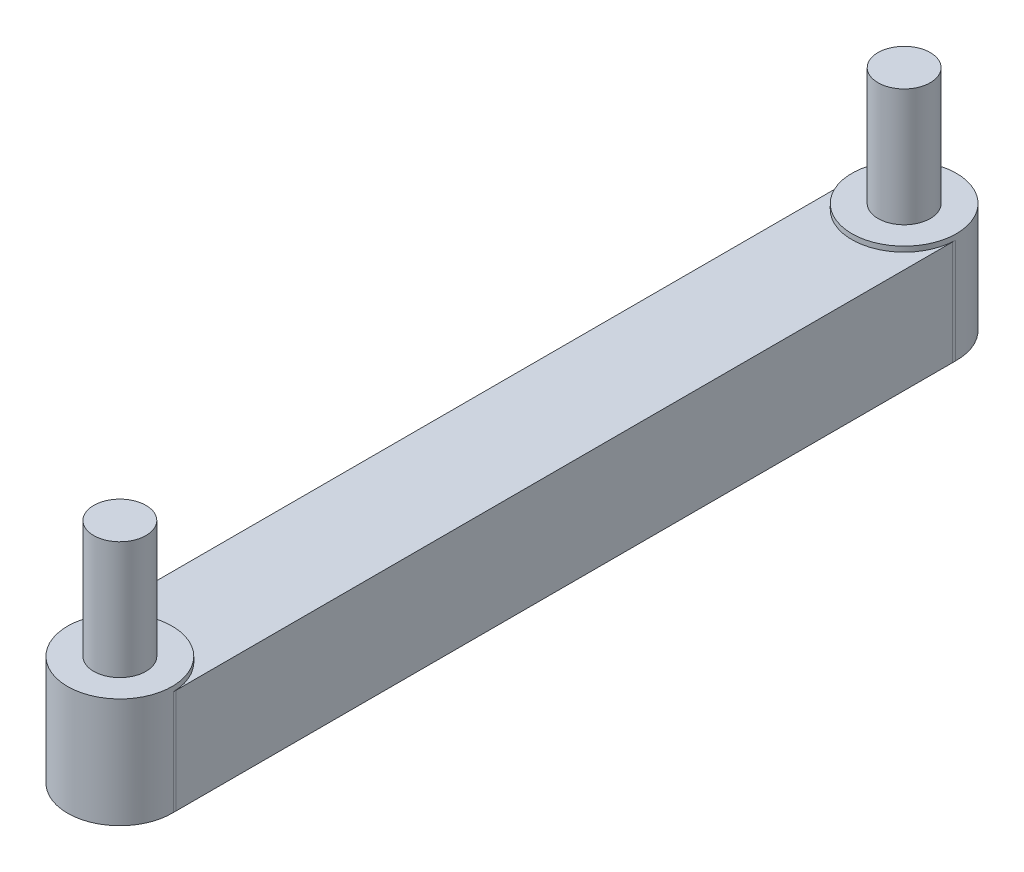
SolidWorks part; units mm, degrees
ref_plane "Ebene vorne" through (0, 0, 0) normal (0, 0, 1) x (1, 0, 0)
ref_plane "Ebene oben" through (0, 0, 0) normal (0, 1, 0) x (1, 0, 0)
ref_plane "Ebene rechts" through (0, 0, 0) normal (1, 0, 0) x (0, 0, -1)
sketch "Skizze1" plane through (0, 0, 0) normal (0, 0, 1) x (1, 0, 0)
  line L1 (-2, 2) -> (2, 2)
  line L2 (-2, 2) -> (-2, -2)
  line L3 (-2, -2) -> (2, -2)
  line L4 (2, 2) -> (2, -2)
  line L5 (-2, 2) -> (2, -2) construction
  line L6 (-2, -2) -> (2, 2) construction
  point P0 (0, 0)
  dimension "D1" = 4
  dimension "D2" = 4
extrude "Aufsatz-Linear austragen1" add sketch "Skizze1" along normal blind 29.7
sketch "Skizze2" plane through (0, 0, 0) normal (0, 1, 0) x (1, 0, 0)
  line L0 (0, -29.7) -> (0, 0) construction
  line L1 (2, -29.7) -> (-2, -29.7) construction
  circle A0 centre (0, -29.85) radius 2
  circle A2 centre (0, 0.15) radius 2
  point P9 (0, -14.85)
  dimension "D1" = 15
  dimension "D2" = 15
extrude "Aufsatz-Linear austragen2" add sketch "Skizze2" against normal blind 4 and the other way blind 0.2 from offset 2
sketch "Skizze3" plane through (0, 2.2, 0) normal (0, 1, 0) x (1, 0, 0)
  circle A0 centre (0, -29.85) radius 1
  circle A2 centre (0, 0.15) radius 1
extrude "Aufsatz-Linear austragen4" add sketch "Skizze3" along normal blind 4.5
fillet "Verrundung1" radius 2 4 edges at (-1.9944, 0, 29.7) (1.9944, 0, 29.7) (-1.9944, 0, 0) (1.9944, 0, 0)
